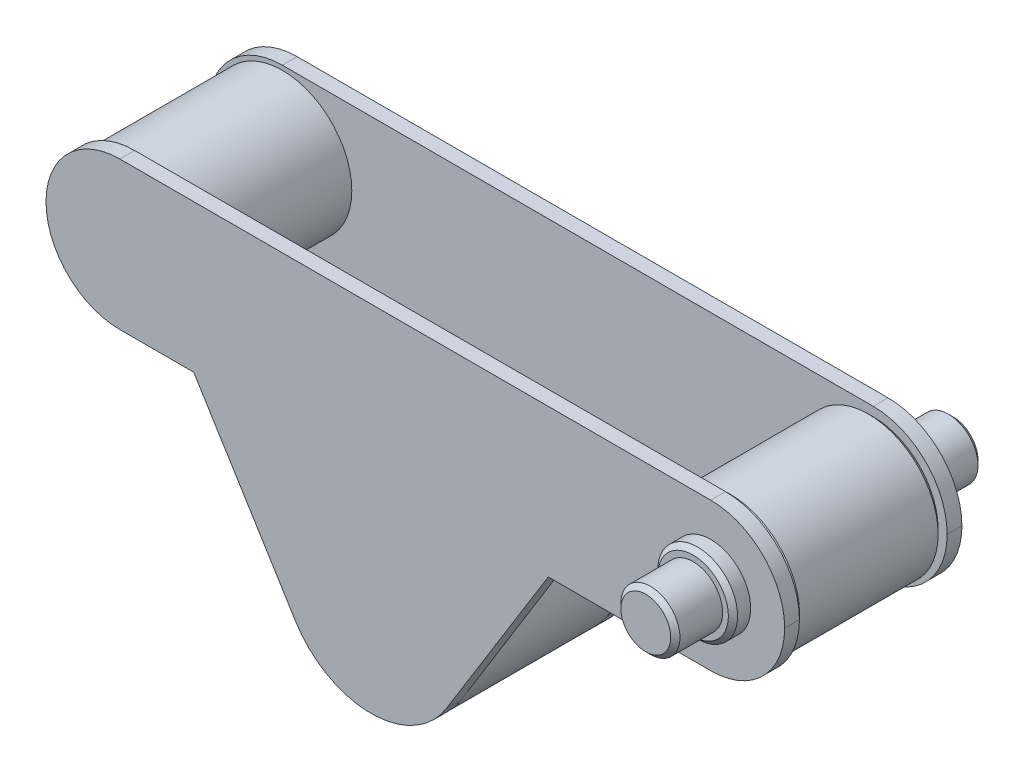
SolidWorks part; units mm, degrees
material "Сталь 3 ГОСТ 535-88"
ref_plane "Спереди" through (0, 0, 0) normal (0, 0, 1) x (1, 0, 0)
ref_plane "Сверху" through (0, 0, 0) normal (0, 1, 0) x (1, 0, 0)
ref_plane "Справа" through (0, 0, 0) normal (1, 0, 0) x (0, 0, -1)
sketch "Эскиз1" plane through (0, 0, 0) normal (1, 0, 0) x (0, 0, -1)
  line L1 (-52, 0) -> (-52, 10)
  line L2 (-52, 10) -> (-36, 10)
  line L3 (-36, 10) -> (-36, 13.5)
  line L4 (-36, 13.5) -> (-25, 13.5)
  line L5 (36, 13.5) -> (36, 10)
  line L6 (36, 10) -> (52, 10)
  line L7 (52, 10) -> (52, 0)
  line L8 (0, 25.8106) -> (0, -23.114) construction
  line L9 (-71.1264, 0) -> (85.8599, 0) construction
  line L10 (-52, 0) -> (52, 0)
  line L11 (25, 13.5) -> (36, 13.5)
  line L13 (25, 13.5) -> (25, 23.5)
  line L14 (25, 23.5) -> (-25, 23.5)
  line L15 (-25, 13.5) -> (-25, 23.5)
  point P12 (52, 5)
  dimension "D1" = 20
  dimension "D2" = 27
  dimension "D3" = 104
  dimension "D4" = 72
  dimension "D5" = 10
  dimension "D6" = 50
revolve "Повернуть1" add sketch "Эскиз1" angle 360 about L9
chamfer "Фаска1" distance 1.56 angle 45 6 edges at (10, 0, 52) (13.5, 0, 36) (10, 0, -52) (23.5, 0, 25) (23.5, 0, -25) (13.5, 0, -36)
sketch "Эскиз2" plane through (0, 0, -25) normal (0, 0, -1) x (-1, 0, 0)
  line L0 (-25, -25) -> (-25, 25)
  line L1 (-25, 25) -> (225, 25)
  line L2 (-25, -25) -> (55, -25)
  line L3 (55, -25) -> (89.4828, -80.7757)
  line L5 (140.5172, -80.7757) -> (175, -25)
  line L6 (175, -25) -> (225, -25)
  line L7 (225, -25) -> (225, 25)
  line L8 (-40.7297, 0) -> (66.8826, 0) construction
  line L9 (115, -95) -> (115, 11.3994) construction
  circle A0 centre (0, 0) radius 13.5 construction
  circle A1 centre (0, 0) radius 13.5
  arc A2 (89.4828, -80.7757) -> (140.5172, -80.7757) centre (115, -65) ccw
  point P6 (142.1605, -95)
  point P9 (0, 0)
  point P19 (0, 0)
  dimension "D6" = 120
  dimension "D4" = 30
  dimension "D1" = 50
  dimension "D2" = 25
  dimension "D3" = 250
  dimension "D5" = 50
  dimension "D7" = 80
extrude "Бобышка-Вытянуть1" add sketch "Эскиз2" along normal blind 5 separate body
fillet "Скругление1" radius 25 4 edges at (25, -25, -27.5) (25, 25, -27.5) (-225, -25, -27.5) (-225, 25, -27.5)
mirror "Зеркальное отражение1" about plane through (0, 0, 0) normal (0, 0, 1) of bodies 104
sketch "Эскиз3" plane through (0, 0, -25) normal (0, 0, 1) x (1, 0, 0)
  arc A1 (-140.5172, -80.7757) -> (-89.4828, -80.7757) centre (-115, -65) ccw construction
  circle A2 centre (-115, -65) radius 30
  point P7 (-85.4147, -60.0291)
  point P9 (0, 0)
extrude "Бобышка-Вытянуть2" add sketch "Эскиз3" along normal up to surface (50 mm away) separate body up to face at (-106, -22.5776, 25)
sketch "Эскиз4" plane through (0, 0, -25) normal (0, 0, 1) x (1, 0, 0)
  circle A0 centre (-200, 0) radius 23.5
  arc A1 (-200, 25) -> (-225, 0) centre (-200, 0) ccw construction
  dimension "D1" = 47
extrude "Бобышка-Вытянуть3" add sketch "Эскиз4" along normal up to surface (50 mm away) separate body up to face at (-106, -22.5776, 25)
